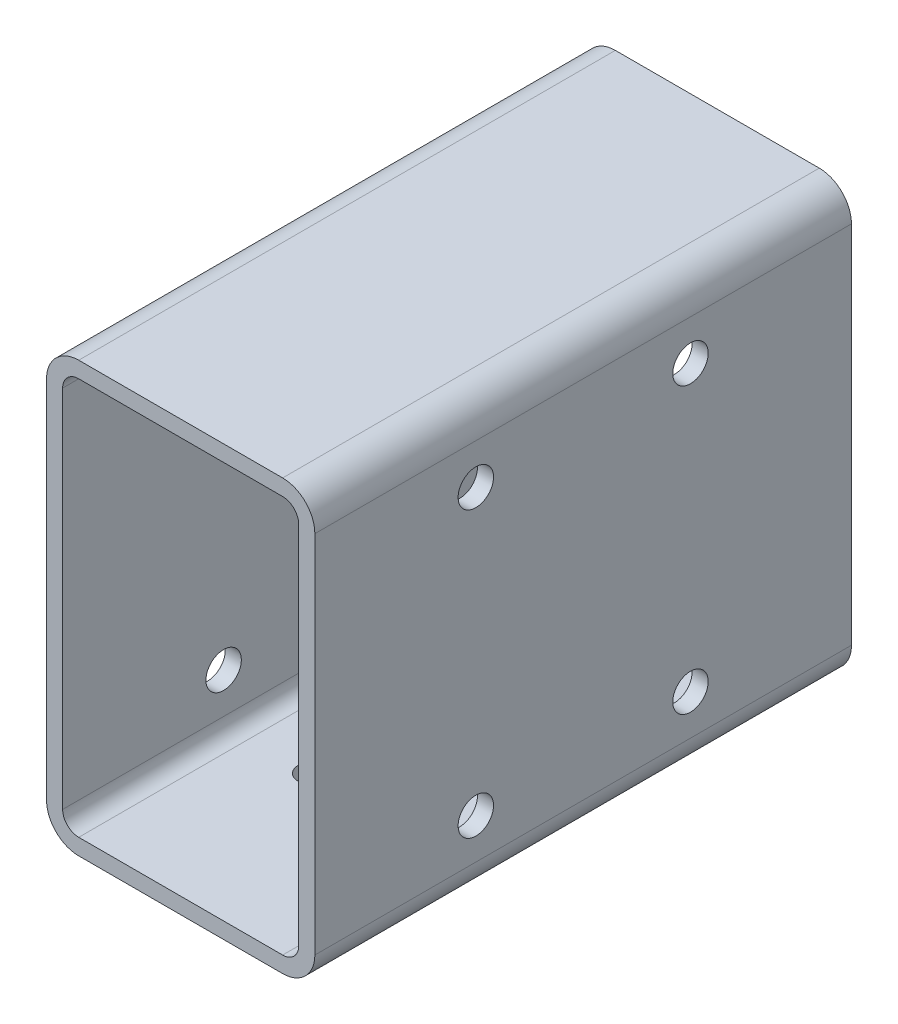
SolidWorks part; units mm, degrees
material "Plain Carbon Steel"
ref_plane "Front Plane" through (0, 0, 0) normal (0, 0, 1) x (1, 0, 0)
ref_plane "Top Plane" through (0, 0, 0) normal (0, 1, 0) x (1, 0, 0)
ref_plane "Right Plane" through (0, 0, 0) normal (1, 0, 0) x (0, 0, -1)
sketch "Sketch1" plane through (0, 0, 0) normal (0, 0, 1) x (1, 0, 0)
  line L0 (19, 40) -> (-19, 40)
  line L1 (19, -37) -> (-19, -37)
  line L2 (22, -34) -> (22, 34)
  line L3 (19, 37) -> (-19, 37)
  line L4 (-22, -34) -> (-22, 34)
  line L5 (22, -37) -> (-22, 37) construction
  line L6 (22, 37) -> (-22, -37) construction
  line L7 (-25, -34) -> (-25, 34)
  line L8 (19, -40) -> (-19, -40)
  line L9 (25, -34) -> (25, 34)
  line L10 (22, -37) -> (-22, -37) construction
  line L11 (22, -37) -> (22, 37) construction
  line L12 (-22, -37) -> (-22, 37) construction
  line L13 (22, 37) -> (-22, 37) construction
  line L14 (-25, -40) -> (-25, 40) construction
  line L15 (25, -40) -> (-25, -40) construction
  line L16 (25, -40) -> (25, 40) construction
  line L17 (25, 40) -> (-25, 40) construction
  arc A0 (19, -37) -> (22, -34) centre (19, -34) ccw
  arc A1 (-19, -37) -> (-22, -34) centre (-19, -34) cw
  arc A2 (-19, 37) -> (-22, 34) centre (-19, 34) ccw
  arc A3 (22, 34) -> (19, 37) centre (19, 34) ccw
  arc A4 (-25, -34) -> (-19, -40) centre (-19, -34) ccw
  arc A5 (19, -40) -> (25, -34) centre (19, -34) ccw
  arc A6 (19, 40) -> (25, 34) centre (19, 34) cw
  arc A7 (-19, 40) -> (-25, 34) centre (-19, 34) ccw
  point P0 (0, 0)
  dimension "D4" = 3
  dimension "D5" = 6
  dimension "D1" = 50
  dimension "D2" = 80
  dimension "D3" = 3
extrude "Boss-Extrude1" add sketch "Sketch1" along normal mid plane 100
sketch "Sketch2" plane through (-25, 0, 0) normal (-1, 0, 0) x (0, 0, 1)
  line L1 (20, -26.5) -> (-20, -26.5) construction
  line L2 (20, -26.5) -> (20, 26.5) construction
  line L3 (20, 26.5) -> (-20, 26.5) construction
  line L4 (-20, -26.5) -> (-20, 26.5) construction
  line L5 (20, -26.5) -> (-20, 26.5) construction
  line L6 (20, 26.5) -> (-20, -26.5) construction
  circle A0 centre (-20, 26.5) radius 3.3
  circle A1 centre (20, 26.5) radius 3.3
  circle A2 centre (20, -26.5) radius 3.3
  circle A3 centre (-20, -26.5) radius 3.3
  point P0 (0, 0)
  dimension "D3" = 6.6
  dimension "D1" = 40
  dimension "D2" = 53
extrude "Cut-Extrude1" cut sketch "Sketch2" against normal through all
sketch "Sketch3" plane through (0, -37, 0) normal (0, 1, 0) x (1, 0, 0)
  line L0 (0, 0) -> (3.6, 0) construction
  line L1 (25, -50) -> (25, 50) construction
  line L2 (14.85, 18) -> (-7.65, 18) construction
  line L3 (14.85, 18) -> (14.85, -18) construction
  line L4 (14.85, -18) -> (-7.65, -18) construction
  line L5 (-7.65, 18) -> (-7.65, -18) construction
  line L6 (14.85, 18) -> (-7.65, -18) construction
  line L7 (14.85, -18) -> (-7.65, 18) construction
  line L8 (-25, -50) -> (-25, 50) construction
  circle A0 centre (-7.65, 0) radius 2.5
  circle A1 centre (-7.65, 18) radius 2.5
  circle A2 centre (-7.65, -18) radius 2.5
  circle A3 centre (14.85, 18) radius 2.5
  circle A4 centre (14.85, -18) radius 2.5
  dimension "D1" = 5
  dimension "D2" = 36
  dimension "D4" = 10.15
  dimension "D3" = 17.35
extrude "Cut-Extrude2" cut sketch "Sketch3" against normal through all
sketch "Sketch4" [suppressed] plane through (0, 0, 0) normal (0, 0, 1) x (1, 0, 0)
  line L0 (50, -44) -> (50, 44) construction
  line L1 (44, -50) -> (-44, -50) construction
  line L2 (-50, -44) -> (-50, 44) construction
  line L3 (44, 50) -> (-44, 50) construction
  line L4 (47, -44) -> (47, 44) construction
  line L5 (44, -47) -> (-44, -47) construction
  line L6 (-47, -44) -> (-47, 44) construction
  line L7 (44, 47) -> (-44, 47) construction
  line L8 (50, -44) -> (50, 44)
  line L9 (44, -50) -> (-44, -50)
  line L10 (-50, -44) -> (-50, 44)
  line L11 (44, 50) -> (-44, 50)
  line L12 (47, -44) -> (47, 44)
  line L13 (44, -47) -> (-44, -47)
  line L14 (-47, -44) -> (-47, 44)
  line L15 (44, 47) -> (-44, 47)
  arc A0 (50, 44) -> (44, 50) centre (44, 44) ccw construction
  arc A1 (44, -50) -> (50, -44) centre (44, -44) ccw construction
  arc A2 (-50, -44) -> (-44, -50) centre (-44, -44) ccw construction
  arc A3 (-44, 50) -> (-50, 44) centre (-44, 44) ccw construction
  arc A4 (47, 44) -> (44, 47) centre (44, 44) ccw construction
  arc A5 (44, -47) -> (47, -44) centre (44, -44) ccw construction
  arc A6 (-47, -44) -> (-44, -47) centre (-44, -44) ccw construction
  arc A7 (-44, 47) -> (-47, 44) centre (-44, 44) ccw construction
  arc A8 (50, 44) -> (44, 50) centre (44, 44) ccw
  arc A9 (44, -50) -> (50, -44) centre (44, -44) ccw
  arc A10 (-50, -44) -> (-44, -50) centre (-44, -44) ccw
  arc A11 (-44, 50) -> (-50, 44) centre (-44, 44) ccw
  arc A12 (47, 44) -> (44, 47) centre (44, 44) ccw
  arc A13 (44, -47) -> (47, -44) centre (44, -44) ccw
  arc A14 (-47, -44) -> (-44, -47) centre (-44, -44) ccw
  arc A15 (-44, 47) -> (-47, 44) centre (-44, 44) ccw
extrude "Boss-Extrude2" [suppressed] add sketch "Sketch4" along normal mid plane 900
sketch "Sketch5" [suppressed] plane through (0, -50, 0) normal (0, -1, 0) x (1, 0, 0)
  line L0 (0, 275.729) -> (0, 77.6099) construction
  line L1 (7, -22) -> (-7, -22) construction
  line L2 (7, -22) -> (7, 22) construction
  line L3 (7, 22) -> (-7, 22) construction
  line L4 (-7, -22) -> (-7, 22) construction
  line L5 (7, -22) -> (-7, 22) construction
  line L6 (7, 22) -> (-7, -22) construction
  line L7 (-44, 450) -> (44, 450) construction
  line L8 (7, 388) -> (-7, 388) construction
  line L9 (7, 388) -> (7, 432) construction
  line L10 (7, 432) -> (-7, 432) construction
  line L11 (-7, 388) -> (-7, 432) construction
  line L12 (7, 388) -> (-7, 432) construction
  line L13 (7, 432) -> (-7, 388) construction
  line L14 (-122.9838, 0) -> (91.0788, 0) construction
  circle A0 centre (-7, 22) radius 3
  circle A1 centre (7, 22) radius 3
  circle A2 centre (-7, -22) radius 3
  circle A3 centre (7, -22) radius 3
  circle A4 centre (-7, 432) radius 3
  circle A5 centre (7, 432) radius 3
  circle A6 centre (-7, 388) radius 3
  circle A7 centre (7, 388) radius 3
  circle A8 centre (0, 410) radius 3
  circle A9 centre (7, -432) radius 3
  circle A10 centre (-7, -432) radius 3
  circle A11 centre (-7, -388) radius 3
  circle A12 centre (7, -388) radius 3
  circle A13 centre (0, -410) radius 3
  point P0 (0, 0)
  point P11 (0, 410)
  dimension "D1" = 6
  dimension "D2" = 14
  dimension "D3" = 44
  dimension "D4" = 18
extrude "Cut-Extrude3" [suppressed] cut sketch "Sketch5" against normal blind 20
sketch "Sketch6" [suppressed] plane through (0, 0, 0) normal (0, 0, 1) x (1, 0, 0)
  line L4 (22, -34) -> (22, 34)
  line L5 (-19, -37) -> (19, -37)
  line L6 (-22, 34) -> (-22, -34)
  line L7 (19, 37) -> (-19, 37)
  line L8 (22, -34) -> (22, 34)
  line L9 (-19, -37) -> (19, -37)
  line L10 (-22, 34) -> (-22, -34)
  line L11 (19, 37) -> (-19, 37)
  line L12 (19, 40) -> (-19, 40)
  line L13 (25, -34) -> (25, 34)
  line L14 (-19, -40) -> (19, -40)
  line L15 (-25, 34) -> (-25, -34)
  line L16 (19, 40) -> (-19, 40)
  line L17 (25, -34) -> (25, 34)
  line L18 (-19, -40) -> (19, -40)
  line L19 (-25, 34) -> (-25, -34)
  arc A4 (19, -37) -> (22, -34) centre (19, -34) ccw
  arc A5 (-22, -34) -> (-19, -37) centre (-19, -34) ccw
  arc A6 (-19, 37) -> (-22, 34) centre (-19, 34) ccw
  arc A7 (22, 34) -> (19, 37) centre (19, 34) ccw
  arc A8 (19, -37) -> (22, -34) centre (19, -34) ccw
  arc A9 (-22, -34) -> (-19, -37) centre (-19, -34) ccw
  arc A10 (-19, 37) -> (-22, 34) centre (-19, 34) ccw
  arc A11 (22, 34) -> (19, 37) centre (19, 34) ccw
  arc A12 (-19, 40) -> (-25, 34) centre (-19, 34) ccw
  arc A13 (25, 34) -> (19, 40) centre (19, 34) ccw
  arc A14 (19, -40) -> (25, -34) centre (19, -34) ccw
  arc A15 (-25, -34) -> (-19, -40) centre (-19, -34) ccw
  arc A16 (-19, 40) -> (-25, 34) centre (-19, 34) ccw
  arc A17 (25, 34) -> (19, 40) centre (19, 34) ccw
  arc A18 (19, -40) -> (25, -34) centre (19, -34) ccw
  arc A19 (-25, -34) -> (-19, -40) centre (-19, -34) ccw
  dimension "D1" = 0
  dimension "D2" = 0
extrude "Boss-Extrude3" [suppressed] add sketch "Sketch6" along normal mid plane 1200
sketch "Sketch7" [suppressed] plane through (-25, 0, 0) normal (-1, 0, 0) x (0, 0, 1)
  line L0 (0, 216.5319) -> (0, -154.0504) construction
  line L1 (-437.1299, 0) -> (-275.6774, 0) construction
  line L2 (-600, 34) -> (-600, -34) construction
  line L3 (-568, 22) -> (-582, 22) construction
  line L4 (-568, 22) -> (-568, -22) construction
  line L5 (-568, -22) -> (-582, -22) construction
  line L6 (-582, 22) -> (-582, -22) construction
  line L7 (-568, 22) -> (-582, -22) construction
  line L8 (-568, -22) -> (-582, 22) construction
  circle A0 centre (-582, 22) radius 3
  circle A1 centre (-568, 22) radius 3
  circle A2 centre (-568, -22) radius 3
  circle A3 centre (-582, -22) radius 3
  circle A4 centre (568, -22) radius 3
  circle A5 centre (582, -22) radius 3
  circle A6 centre (582, 22) radius 3
  circle A7 centre (568, 22) radius 3
  point P1 (-575, 0)
  dimension "D1" = 6
  dimension "D2" = 14
  dimension "D3" = 44
  dimension "D4" = 18
extrude "Cut-Extrude4" [suppressed] cut sketch "Sketch7" against normal through all and the other way through all
sketch "Sketch8" [suppressed] plane through (-25, 0, 0) normal (-1, 0, 0) x (0, 0, 1)
  line L0 (-582, 22) -> (-568, -22) construction
  line L1 (0, 84.5802) -> (0, -115.7286) construction
  circle A0 centre (-575, 0) radius 3
  circle A1 centre (-568, 22) radius 3 construction
  circle A2 centre (575, 0) radius 3
extrude "Cut-Extrude5" [suppressed] cut sketch "Sketch8" against normal blind 20
sketch "Sketch9" [suppressed] plane through (0, 0, 0) normal (0, 0, 1) x (1, 0, 0)
  line L4 (22, -34) -> (22, 34)
  line L5 (-19, -37) -> (19, -37)
  line L6 (-22, 34) -> (-22, -34)
  line L7 (19, 37) -> (-19, 37)
  line L8 (22, -34) -> (22, 34)
  line L9 (-19, -37) -> (19, -37)
  line L10 (-22, 34) -> (-22, -34)
  line L11 (19, 37) -> (-19, 37)
  line L12 (19, 40) -> (-19, 40)
  line L13 (25, -34) -> (25, 34)
  line L14 (-19, -40) -> (19, -40)
  line L15 (-25, 34) -> (-25, -34)
  line L16 (19, 40) -> (-19, 40)
  line L17 (25, -34) -> (25, 34)
  line L18 (-19, -40) -> (19, -40)
  line L19 (-25, 34) -> (-25, -34)
  arc A4 (19, -37) -> (22, -34) centre (19, -34) ccw
  arc A5 (-22, -34) -> (-19, -37) centre (-19, -34) ccw
  arc A6 (-19, 37) -> (-22, 34) centre (-19, 34) ccw
  arc A7 (22, 34) -> (19, 37) centre (19, 34) ccw
  arc A8 (19, -37) -> (22, -34) centre (19, -34) ccw
  arc A9 (-22, -34) -> (-19, -37) centre (-19, -34) ccw
  arc A10 (-19, 37) -> (-22, 34) centre (-19, 34) ccw
  arc A11 (22, 34) -> (19, 37) centre (19, 34) ccw
  arc A12 (-19, 40) -> (-25, 34) centre (-19, 34) ccw
  arc A13 (25, 34) -> (19, 40) centre (19, 34) ccw
  arc A14 (19, -40) -> (25, -34) centre (19, -34) ccw
  arc A15 (-25, -34) -> (-19, -40) centre (-19, -34) ccw
  arc A16 (-19, 40) -> (-25, 34) centre (-19, 34) ccw
  arc A17 (25, 34) -> (19, 40) centre (19, 34) ccw
  arc A18 (19, -40) -> (25, -34) centre (19, -34) ccw
  arc A19 (-25, -34) -> (-19, -40) centre (-19, -34) ccw
  dimension "D1" = 0
  dimension "D2" = 0
extrude "Boss-Extrude4" [suppressed] add sketch "Sketch9" along normal mid plane 1230
sketch "Sketch10" [suppressed] plane through (0, -40, 0) normal (0, -1, 0) x (1, 0, 0)
  line L0 (-413.5216, 0) -> (284.1515, 0) construction
  line L1 (0, 0) -> (0, 35) construction
  line L2 (-19, 35) -> (19, 35) construction
  line L4 (9.225, -32) -> (-9.225, -32) construction
  line L5 (9.225, -32) -> (9.225, 22) construction
  line L6 (9.225, 22) -> (-9.225, 22) construction
  line L7 (-9.225, -32) -> (-9.225, 22) construction
  line L8 (9.225, -32) -> (-9.225, 22) construction
  line L9 (9.225, 22) -> (-9.225, -32) construction
  circle A0 centre (-9.225, 22) radius 3
  circle A1 centre (9.225, 22) radius 3
  circle A2 centre (9.225, -32) radius 3
  circle A3 centre (-9.225, -32) radius 3
  circle A4 centre (9.225, 32) radius 3
  circle A5 centre (-9.225, 32) radius 3
  circle A6 centre (9.225, -22) radius 3
  circle A7 centre (-9.225, -22) radius 3
  point P7 (0, -5)
  dimension "D1" = 6
  dimension "D2" = 18.45
  dimension "D3" = 54
  dimension "D4" = 13
extrude "Cut-Extrude6" [suppressed] cut sketch "Sketch10" against normal blind 20
sketch "Sketch11" [suppressed] plane through (-25, 0, 0) normal (-1, 0, 0) x (0, 0, 1)
  line L1 (20, -26.5) -> (-20, -26.5) construction
  line L2 (20, -26.5) -> (20, 26.5) construction
  line L3 (20, 26.5) -> (-20, 26.5) construction
  line L4 (-20, -26.5) -> (-20, 26.5) construction
  line L5 (20, -26.5) -> (-20, 26.5) construction
  line L6 (20, 26.5) -> (-20, -26.5) construction
  circle A0 centre (-20, 26.5) radius 3
  circle A1 centre (20, 26.5) radius 3
  circle A2 centre (20, -26.5) radius 3
  circle A3 centre (-20, -26.5) radius 3
  point P0 (0, 0)
  dimension "D1" = 6
  dimension "D2" = 53
  dimension "D3" = 40
extrude "Cut-Extrude7" [suppressed] cut sketch "Sketch11" against normal blind 20
sketch "Sketch12" [suppressed] plane through (25, 0, 0) normal (1, 0, 0) x (0, 0, -1)
  line L1 (9.225, -27) -> (-9.225, -27) construction
  line L2 (9.225, -27) -> (9.225, 27) construction
  line L3 (9.225, 27) -> (-9.225, 27) construction
  line L4 (-9.225, -27) -> (-9.225, 27) construction
  line L5 (9.225, -27) -> (-9.225, 27) construction
  line L6 (9.225, 27) -> (-9.225, -27) construction
  circle A0 centre (-9.225, 27) radius 3
  circle A1 centre (9.225, 27) radius 3
  circle A2 centre (9.225, -27) radius 3
  circle A3 centre (-9.225, -27) radius 3
  point P0 (0, 0)
  dimension "D1" = 6
  dimension "D2" = 18.45
  dimension "D3" = 54
extrude "Cut-Extrude8" [suppressed] cut sketch "Sketch12" against normal blind 20
equation "\"length\"= 100"
equation "\"D1@Boss-Extrude1\"=\"length\""
equation "\"D3@Sketch2\"=\"M6_clearence\""
equation "\"D1@Sketch3\"=\"M6_tap\""
equation "\"M5_tap\"=4.2mm"
equation "\"M5_clearence\"=5.5mm"
equation "\"M6_tap\"=5mm"
equation "\"M6_clearence\"=6.6mm"
equation "\"work_area_width\"=1100mm"
equation "\"work_area_depth\"=900mm"
equation "\"D1@Boss-Extrude2\"=\"work_area_depth\""
equation "\"D1@Boss-Extrude3\"=\"work_area_width\" + (50*2)"
equation "\"D1@Boss-Extrude4\"=\"work_area_width\" + 130mm"
equation "\"steel_stock_width\"=80mm"
equation "\"steel_stock_height\"=50mm"
equation "\"D1@Sketch1\"=\"steel_stock_height\""
equation "\"D2@Sketch1\"=\"steel_stock_width\""
equation "\"steel_stock_wall_thickness\"=3mm"
equation "\"D3@Sketch1\"=\"steel_stock_wall_thickness\""
equation "\"steel_stock_radius\"=6mm"
